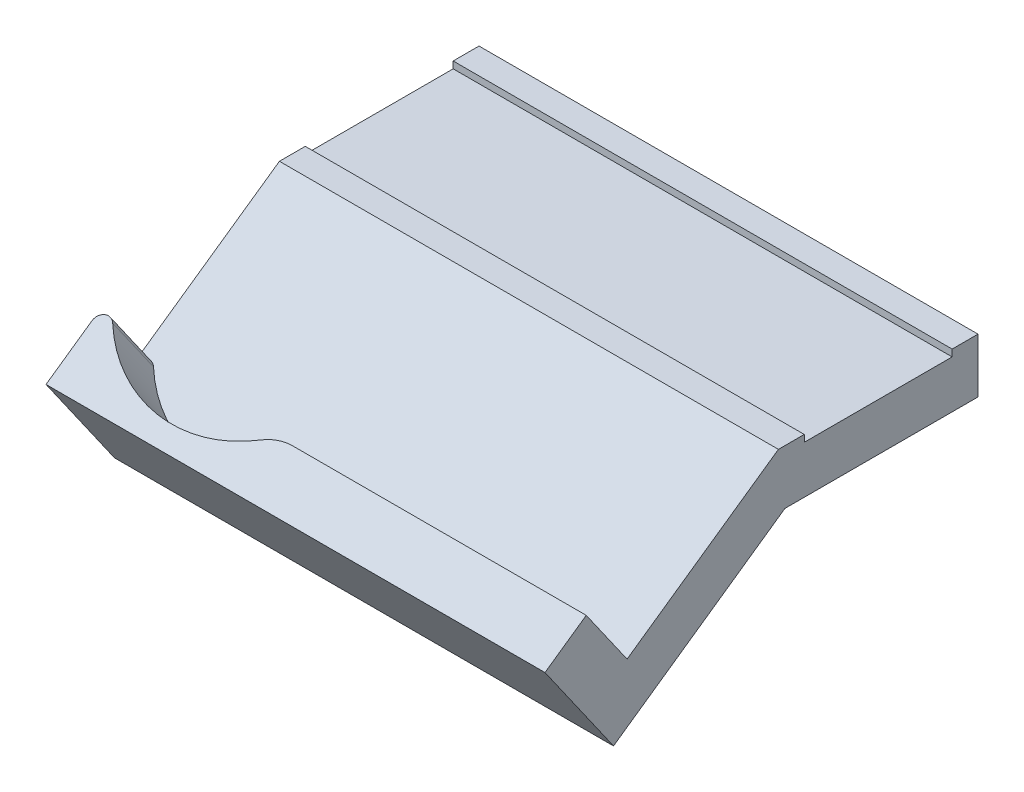
SolidWorks part; units mm, degrees
ref_plane "Front Plane" through (0, 0, 0) normal (0, 0, 1) x (1, 0, 0)
ref_plane "Top Plane" through (0, 0, 0) normal (0, 1, 0) x (1, 0, 0)
ref_plane "Right Plane" through (0, 0, 0) normal (1, 0, 0) x (0, 0, -1)
sketch "Sketch1" plane through (0, 0, 0) normal (0, 1, 0) x (1, 0, 0)
  line L1 (0, 29) -> (55, 29)
  line L2 (0, 29) -> (0, 0)
  line L3 (0, 0) -> (55, 0)
  line L4 (55, 29) -> (55, 0)
  dimension "D1" = 55
  dimension "D2" = 29
extrude "Boss-Extrude1" add sketch "Sketch1" along normal blind 50 contours L2 L3 L4 L1
sketch "Sketch4" plane through (55, 0, 0) normal (1, 0, 0) x (0, 0, -1)
  line L0 (29, 0) -> (0, 0) construction
  line L1 (-21.6788, 50.9576) -> (19.2788, 79.6364)
  line L2 (-21.6788, 50.9576) -> (7, 10)
  line L3 (7, 10) -> (47.9576, 38.6788)
  line L4 (19.2788, 79.6364) -> (47.9576, 38.6788)
  line L5 (0, 50) -> (0, 0) construction
  dimension "D1" = 50
  dimension "D2" = 50
  dimension "D3" = 10
  dimension "D4" = 7
  dimension "D5" = 35
extrude "Cut-Extrude1" cut sketch "Sketch4" against normal blind 50
sketch "Sketch5" plane through (55, 0, 0) normal (1, 0, 0) x (0, 0, -1)
  line L0 (0, 19.997) -> (0, 0) construction
  line L1 (-11.4273, 18.8824) -> (-3.2358, 24.6182)
  line L2 (-11.4273, 18.8824) -> (-5.6915, 10.6909)
  line L3 (-5.6915, 10.6909) -> (2.5, 16.4267)
  line L4 (-3.2358, 24.6182) -> (2.5, 16.4267)
  line L5 (0, 19.997) -> (7, 10) construction
  dimension "D1" = 10
  dimension "D2" = 10
  dimension "D3" = 2.5
extrude "Cut-Extrude2" cut sketch "Sketch5" against normal through all
sketch "Sketch12" plane through (55, 0, 0) normal (1, 0, 0) x (0, 0, -1)
  line L0 (2.5, 16.4267) -> (7, 10)
  line L1 (7, 10) -> (7.8192, 10.5736)
  line L2 (7, 10) -> (29, 25.4046) construction
  line L3 (7.8192, 10.5736) -> (3.3192, 17.0002)
  line L4 (3.3192, 17.0002) -> (2.5, 16.4267)
  dimension "D1" = 1
extrude "Boss-Extrude2" add sketch "Sketch12" against normal through all contours L3 L4 L0 L1
sketch "Sketch6" plane through (0, 3.4212, 2.3955) normal (0, 0.8192, 0.5736) x (1, 0, 0)
  line L0 (55, 8.4179) -> (0, 8.4179) construction
  line L3 (0, 52.4342) -> (0, 28.6788) construction
  circle A0 centre (12, 22.9179) radius 13.75
  dimension "D1" = 27.5
  dimension "D2" = 14.5
  dimension "D3" = 12
extrude "Cut-Extrude3" cut sketch "Sketch6" along normal through all
ref_axis "Axis2" through (12, 42.1941, 1.567) along (0, -0.8192, -0.5736)
sketch "Sketch7" plane through (55, 0, 0) normal (1, 0, 0) x (0, 0, -1)
  line L0 (0, 14.6761) -> (6.3789, 19.1427)
  line L1 (21.8766, 20.4167) -> (10.8789, 12.716) construction
  line L2 (6.3789, 19.1427) -> (10.8789, 12.716)
  line L3 (10.8789, 12.716) -> (85.0856, 64.6761)
  line L4 (85.0856, 64.6761) -> (25.4084, 64.6761)
  line L5 (25.4084, 64.6761) -> (0, 64.6761)
  line L6 (0, 64.6761) -> (0, 14.6761)
  line L7 (10.8789, 12.716) -> (0, 28.2526) construction
  line L8 (7.8192, 10.5736) -> (29, 25.4046) construction
  dimension "D1" = 50
extrude "Cut-Extrude4" cut sketch "Sketch7" against normal through all contours L5 L6 L0 L2 L3 L4
sketch "Sketch8" plane through (0, 0, 0) normal (0, 1, 0) x (1, 0, 0)
  line L0 (12, -1.567) -> (12, 11.76) construction
  line L3 (55, 29) -> (0, 29) construction
  circle A0 centre (25.75, 30.5) radius 6
  dimension "D1" = 12
  dimension "D3" = 1.5
  dimension "D2" = 13.75
extrude "Cut-Extrude5" cut sketch "Sketch8" along normal through all contours A0
sketch "Sketch9" plane through (55, 0, 0) normal (1, 0, 0) x (0, 0, -1)
  line L0 (24.5, 22.2536) -> (29, 22.2536)
  line L1 (29, 25.4046) -> (29, 0) construction
  line L2 (29, 22.2536) -> (29, 25.4046)
  line L3 (29, 25.4046) -> (24.5, 22.2536)
extrude "Cut-Extrude6" cut sketch "Sketch9" against normal through all
sketch "Sketch10" plane through (0, 0, 0) normal (0, 1, 0) x (1, 0, 0)
  line L0 (0, 24.5) -> (25.75, 24.5) construction
  line L1 (55, 24.5) -> (0, 24.5)
  line L2 (55, 24.5) -> (55, 29)
  line L3 (55, 29) -> (0, 29)
  line L4 (0, 24.5) -> (0, 29)
  line L5 (0, 24.5) -> (0, 10.8789) construction
extrude "Cut-Extrude7" cut sketch "Sketch10" along normal through all
fillet "Fillet5" radius 1 1 edges at (0, 15.9293, -8.6289) tangent propagation no
fillet "Fillet6" radius 5 1 edges at (20.9387, 13.7869, -5.5692)
sketch "Sketch16" plane through (55, 0, 0) normal (1, 0, 0) x (0, 0, -1)
  line L0 (24.5, 15.7536) -> (7.554, 3.8879)
  line L1 (24.5, 22.2536) -> (24.5, 0) construction
  line L2 (7.554, 3.8879) -> (0, 14.6761)
  line L3 (0, 14.6761) -> (0, 0)
  line L4 (0, 0) -> (24.5, 0)
  line L5 (24.5, 0) -> (24.5, 15.7536)
  line L6 (7.8192, 10.5736) -> (24.5, 22.2536) construction
  line L7 (24.5, 0) -> (0, 0) construction
  dimension "D1" = 6.5
extrude "Cut-Extrude8" cut sketch "Sketch16" against normal through all
sketch "Sketch17" plane through (0, 0, -24.5) normal (0, 0, -1) x (-1, 0, 0)
  line L1 (-55, 22.2536) -> (0, 22.2536)
  line L2 (-55, 22.2536) -> (-55, 16.2536)
  line L3 (-55, 16.2536) -> (0, 16.2536)
  line L4 (0, 22.2536) -> (0, 16.2536)
  dimension "D1" = 6
extrude "Boss-Extrude4" add sketch "Sketch17" along normal blind 22
sketch "Sketch18" plane through (55, 0, 0) normal (1, 0, 0) x (0, 0, -1)
  line L0 (16.027, 9.8208) -> (33.783, 22.2536)
  line L1 (24.5, 15.7536) -> (7.554, 3.8879) construction
  line L2 (46.5, 22.2536) -> (24.5, 22.2536) construction
  line L3 (33.783, 22.2536) -> (24.5, 22.2536)
  line L4 (24.5, 22.2536) -> (12.973, 14.1823)
  line L5 (7.8192, 10.5736) -> (24.5, 22.2536) construction
  line L6 (12.973, 14.1823) -> (16.027, 9.8208)
extrude "Boss-Extrude5" add sketch "Sketch18" against normal up to surface (55 mm away) contours L0 L3 L4 L6 up to face at (0, 15.541, -21.9123)
sketch "Sketch19" plane through (0, 22.2536, 0) normal (0, 1, 0) x (1, 0, 0)
  line L0 (0, 46.5) -> (0, 24.5) construction
  line L1 (0, 43.65) -> (55, 43.65)
  line L2 (0, 43.65) -> (0, 27.35)
  line L3 (0, 27.35) -> (55, 27.35)
  line L4 (55, 43.65) -> (55, 27.35)
  line L5 (55, 46.5) -> (55, 24.5) construction
  point P8 (0, 35.5)
  dimension "D1" = 16.3
extrude "Cut-Extrude9" cut sketch "Sketch19" against normal blind 0.75
sketch "Sketch20" plane through (55, 0, 0) normal (1, 0, 0) x (0, 0, -1)
  line L0 (0, 14.6761) -> (-1.2287, 13.8158)
  line L1 (-1.2287, 13.8158) -> (6.3253, 3.0276)
  line L2 (6.3253, 3.0276) -> (7.554, 3.8879)
  line L3 (7.554, 3.8879) -> (0, 14.6761)
  line L4 (0, 14.6761) -> (3.3192, 17.0002) construction
  line L5 (25.2141, 16.2536) -> (7.554, 3.8879) construction
  dimension "D1" = 1.5
extrude "Boss-Extrude6" add sketch "Sketch20" against normal up to surface (55 mm away) contours L1 L2 L3 L0 up to face at (0, 17.615, -26.2556)
